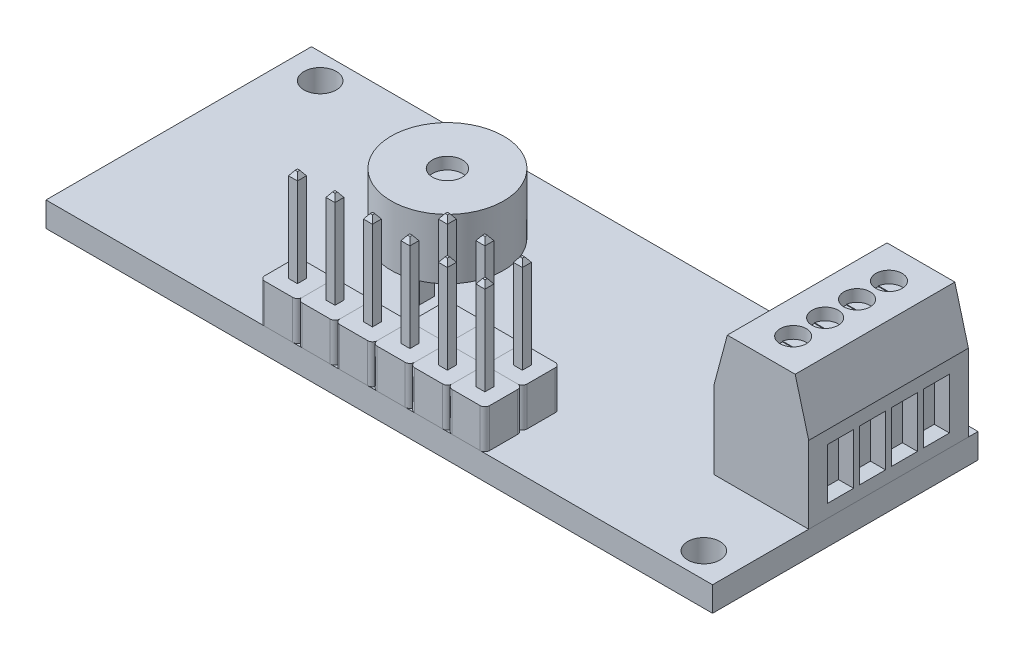
SolidWorks part; units mm, degrees
ref_plane "Front Plane" through (0, 0, 0) normal (0, 0, 1) x (1, 0, 0)
ref_plane "Top Plane" through (0, 0, 0) normal (0, 1, 0) x (1, 0, 0)
ref_plane "Right Plane" through (0, 0, 0) normal (1, 0, 0) x (0, 0, -1)
ref_axis "Axis1" through (-88.99, 0, 0) along (1, 0, 0)
ref_axis "Axis2" through (0, 55, 0) along (0, -1, 0)
ref_axis "Axis3" through (0, 0, 55) along (0, 0, -1)
ref_point "Point1"
sketch "Sketch1" plane through (0, 0, 0) normal (0, 1, 0) x (1, 0, 0)
  line L1 (-22.225, -8.8519) -> (22.225, -8.8519)
  line L2 (-22.225, -8.8519) -> (-22.225, 8.8519)
  line L3 (-22.225, 8.8519) -> (22.225, 8.8519)
  line L4 (22.225, -8.8519) -> (22.225, 8.8519)
  line L5 (-22.225, -8.8519) -> (22.225, 8.8519) construction
  line L6 (-22.225, 8.8519) -> (22.225, -8.8519) construction
  point P0 (0, 0)
  dimension "D1" = 44.45
  dimension "D2" = 17.7038
extrude "Boss-Extrude1" add sketch "Sketch1" along normal mid plane 1.651
sketch "Sketch2" plane through (0, 0.8255, 0) normal (0, 1, 0) x (1, 0, 0)
  line L0 (-21.045, 7.1769) -> (-22.225, 7.1769) construction
  line L1 (-22.225, 8.8519) -> (-22.225, -8.8519) construction
  line L2 (-19.97, 8.2519) -> (-19.97, 8.8519) construction
  line L3 (22.225, 8.8519) -> (-22.225, 8.8519) construction
  line L4 (0, 8.8519) -> (0, 0) construction
  line L5 (0, 0) -> (22.225, 0) construction
  line L6 (22.225, -8.8519) -> (22.225, 8.8519) construction
  circle A0 centre (-19.97, 7.1769) radius 1.075
  circle A3 centre (19.97, -7.1769) radius 1.075
  dimension "D1" = 2.15
  dimension "D2" = 0.6
  dimension "D3" = 1.18
extrude "Cut-Extrude1" cut sketch "Sketch2" against normal through all both and the other way through all
ref_plane "Plane1" through (0, 0, -8.2119) normal (0, 0, -1) x (-1, 0, 0)
sketch "Sketch3" plane through (0, 0, -8.2119) normal (0, 0, -1) x (-1, 0, 0)
  line L0 (-22.225, 0.8255) -> (-22.225, 5.9555)
  line L1 (-22.225, 5.9555) -> (-21.322, 9.3255)
  line L2 (-21.322, 9.3255) -> (-16.798, 9.3255)
  line L3 (-15.895, 5.9555) -> (-16.798, 9.3255)
  line L4 (-15.895, 5.9555) -> (-15.895, 0.8255)
  line L5 (-22.225, 0.8255) -> (22.225, 0.8255) construction
  line L6 (-22.225, 5.9555) -> (-15.895, 5.9555) construction
  line L7 (-19.06, 9.3255) -> (-19.06, 5.9555) construction
  line L8 (-22.225, 0.8255) -> (-15.895, 0.8255)
  dimension "D1" = 8.5
  dimension "D2" = 6.33
  dimension "D3" = 75
  dimension "D5" = 3.37
extrude "Boss-Extrude2" add sketch "Sketch3" against normal blind 10.65 separate body
sketch "Sketch4" plane through (0, 0.8255, 0) normal (0, 1, 0) x (1, 0, 0)
  line L0 (7.045, -8.8519) -> (7.045, -6.3519)
  line L1 (-22.225, -8.8519) -> (22.225, -8.8519) construction
  line L2 (7.045, -6.3519) -> (4.545, -6.3519)
  line L5 (22.225, -8.8519) -> (22.225, 8.8519) construction
  line L6 (-0.455, -7.6019) -> (2.045, -7.6019) construction
  line L7 (2.045, -7.6019) -> (4.545, -7.6019) construction
  line L8 (4.545, -7.6019) -> (7.045, -7.6019) construction
  line L10 (4.545, -8.8519) -> (4.545, -6.3519)
  line L12 (4.545, -8.8519) -> (7.045, -8.8519)
  point P15 (2.045, -7.6019)
  point P18 (4.545, -7.6019)
  dimension "D1" = 15.18
  dimension "D2" = 2.5
  dimension "D3" = 2.5
extrude "Boss-Extrude3" add sketch "Sketch4" along normal blind 2.599 separate body
sketch "Sketch5" plane through (0, 3.4245, 0) normal (0, 1, 0) x (1, 0, 0)
  line L0 (7.045, -6.3519) -> (4.545, -8.8519) construction
  line L2 (5.495, -7.3019) -> (6.095, -7.3019)
  line L3 (5.495, -7.3019) -> (5.495, -7.9019)
  line L4 (5.495, -7.9019) -> (6.095, -7.9019)
  line L5 (6.095, -7.3019) -> (6.095, -7.9019)
  line L6 (5.495, -7.3019) -> (6.095, -7.9019) construction
  line L7 (5.495, -7.9019) -> (6.095, -7.3019) construction
  point P4 (5.795, -7.6019)
  dimension "D1" = 0.6
  dimension "D2" = 0.6
extrude "Boss-Extrude4" add sketch "Sketch5" along normal blind 6.25 separate body
chamfer "Chamfer1" distance 0.3175 angle 35 4 edges at (5.495, 9.6745, 7.6019) (5.795, 9.6745, 7.3019) (6.095, 9.6745, 7.6019) (5.795, 9.6745, 7.9019) first distance on face at (5.495, 6.5495, 7.6019) first distance on face at (5.795, 6.5495, 7.3019) first distance on face at (6.095, 6.5495, 7.6019) first distance on face at (5.795, 6.5495, 7.9019)
fillet "Fillet1" radius 0.3175 4 edges at (7.045, 2.125, 6.3519) (4.545, 2.125, 6.3519) (7.045, 2.125, 8.8519) (4.545, 2.125, 8.8519)
pattern_linear "LPattern2" count 6 spacing 2.5 along (-1, 0, 0) of bodies 105 104
pattern_linear "LPattern3" count 2 spacing 2.5 along (0, 0, -1) of bodies 105 106 107 112 111 104
sketch "Sketch7" plane through (0, 0.8255, 0) normal (0, 1, 0) x (1, 0, 0)
  line L0 (-7.955, -7.6019) -> (-7.955, 8.8519) construction
  line L1 (-7.955, -6.6694) -> (-7.955, -8.5344) construction
  line L2 (22.225, 8.8519) -> (-22.225, 8.8519) construction
  line L3 (-0.455, -7.6019) -> (-0.455, 8.8519) construction
  line L4 (-0.455, -8.5344) -> (-0.455, -6.6694) construction
  line L5 (0.795, -3.8519) -> (-7.955, -3.8519) construction
  line L6 (1.7275, -3.8519) -> (-0.1375, -3.8519) construction
  circle A0 centre (-4.205, -0.1019) radius 3.75
extrude "Boss-Extrude5" add sketch "Sketch7" along normal blind 6.45 separate body
sketch "Sketch8" plane through (0, 0.8255, 0) normal (0, 1, 0) x (1, 0, 0)
  line L0 (-4.205, -0.1019) -> (-3.079, -0.1019) construction
  line L1 (-4.705, 2.2731) -> (-3.705, 2.2731)
  line L2 (-4.705, 2.2731) -> (-4.705, 1.2731)
  line L3 (-4.705, 1.2731) -> (-3.705, 1.2731)
  line L4 (-3.705, 2.2731) -> (-3.705, 1.2731)
  line L5 (-4.705, 2.2731) -> (-3.705, 1.2731) construction
  line L6 (-4.705, 1.2731) -> (-3.705, 2.2731) construction
  line L7 (-4.205, 1.7731) -> (-4.205, -0.1019) construction
  line L8 (-4.205, 1.7731) -> (-4.205, 3.6481) construction
  line L9 (-4.705, -2.4769) -> (-3.705, -2.4769)
  line L10 (-4.705, -2.4769) -> (-4.705, -1.4769)
  line L11 (-4.705, -1.4769) -> (-3.705, -1.4769)
  line L12 (-3.705, -2.4769) -> (-3.705, -1.4769)
  circle A0 centre (-4.205, -0.1019) radius 3.75 construction
  circle A1 centre (-4.205, -0.1019) radius 3.75
  point P3 (-4.205, 1.7731)
  dimension "D1" = 1
  dimension "D2" = 1
extrude "Cut-Extrude2" cut sketch "Sketch8" along normal blind 2.44
sketch "Sketch9" plane through (0, 7.2755, 0) normal (0, 1, 0) x (1, 0, 0)
  circle A0 centre (-4.205, -0.1019) radius 1
  dimension "D1" = 2
extrude "Cut-Extrude3" cut sketch "Sketch9" against normal blind 0.7937
sketch "Sketch10" plane through (0, 9.3255, 0) normal (0, 1, 0) x (1, 0, 0)
  line L0 (19.06, 8.2119) -> (19.06, 6.0819) construction
  line L1 (16.798, 8.2119) -> (21.322, 8.2119) construction
  line L2 (19.06, 6.0819) -> (19.06, 3.9519) construction
  line L3 (19.06, 3.9519) -> (19.06, 1.8219) construction
  line L4 (19.06, 1.8219) -> (19.06, -0.3081) construction
  line L5 (19.06, -0.3081) -> (19.06, -2.4381) construction
  line L6 (16.798, -2.4381) -> (21.322, -2.4381) construction
  circle A0 centre (19.06, 6.0819) radius 0.875
  circle A1 centre (19.06, 3.9519) radius 0.875
  circle A2 centre (19.06, 1.8219) radius 0.875
  circle A3 centre (19.06, -0.3081) radius 0.875
  point P12 (19.06, 7.1469)
  dimension "D1" = 1.75
extrude "Cut-Extrude4" cut sketch "Sketch10" against normal blind 0.7937
sketch "Sketch11" plane through (22.225, 0, 0) normal (1, 0, 0) x (0, 0, -1)
  line L0 (-2.4381, 3.3905) -> (-0.3081, 3.3905) construction
  line L1 (-2.4381, 5.9555) -> (-2.4381, 0.8255) construction
  line L2 (-0.3081, 3.3905) -> (1.8219, 3.3905) construction
  line L3 (1.8219, 3.3905) -> (3.9519, 3.3905) construction
  line L4 (3.9519, 3.3905) -> (6.0819, 3.3905) construction
  line L5 (6.0819, 3.3905) -> (8.2119, 3.3905) construction
  line L6 (8.2119, 5.9555) -> (8.2119, 0.8255) construction
  line L8 (0.5569, 5.0905) -> (-1.1731, 5.0905)
  line L9 (0.5569, 5.0905) -> (0.5569, 1.6905)
  line L10 (0.5569, 1.6905) -> (-1.1731, 1.6905)
  line L11 (-1.1731, 5.0905) -> (-1.1731, 1.6905)
  line L12 (0.5569, 5.0905) -> (-1.1731, 1.6905) construction
  line L13 (0.5569, 1.6905) -> (-1.1731, 5.0905) construction
  dimension "D1" = 3.4
  dimension "D2" = 1.73
extrude "Cut-Extrude5" cut sketch "Sketch11" against normal blind 0.7937 draft 15
pattern_linear "LPattern4" count 4 spacing 2.13 along (0, 0, -1) of "Cut-Extrude5"
sketch "Sketch12" plane through (0, 8.5318, 0) normal (0, 1, 0) x (1, 0, 0)
  line L0 (19.935, -0.3081) -> (18.185, -0.3081) construction
  line L2 (18.1995, -0.4668) -> (19.9205, -0.4668)
  line L4 (18.1995, -0.1493) -> (19.9205, -0.1493)
  line L6 (18.185, -0.4668) -> (19.935, -0.1493) construction
  line L7 (18.185, -0.1493) -> (19.935, -0.4668) construction
  circle A0 centre (19.06, -0.3081) radius 0.875 construction
  circle A1 centre (19.06, -0.3081) radius 0.875 construction
  arc A2 (19.9205, -0.4668) -> (19.9205, -0.1493) centre (19.06, -0.3081) ccw
  circle A3 centre (19.06, -0.3081) radius 0.875
  arc A4 (18.1995, -0.1493) -> (18.1995, -0.4668) centre (19.06, -0.3081) ccw
  point P7 (19.06, -0.3081)
  dimension "D1" = 0
  dimension "D2" = 0.3175
extrude "Cut-Extrude6" cut sketch "Sketch12" against normal blind 0.0496
pattern_linear "LPattern5" count 4 spacing 2.13 along (0, 0, -1) of "Cut-Extrude6"
